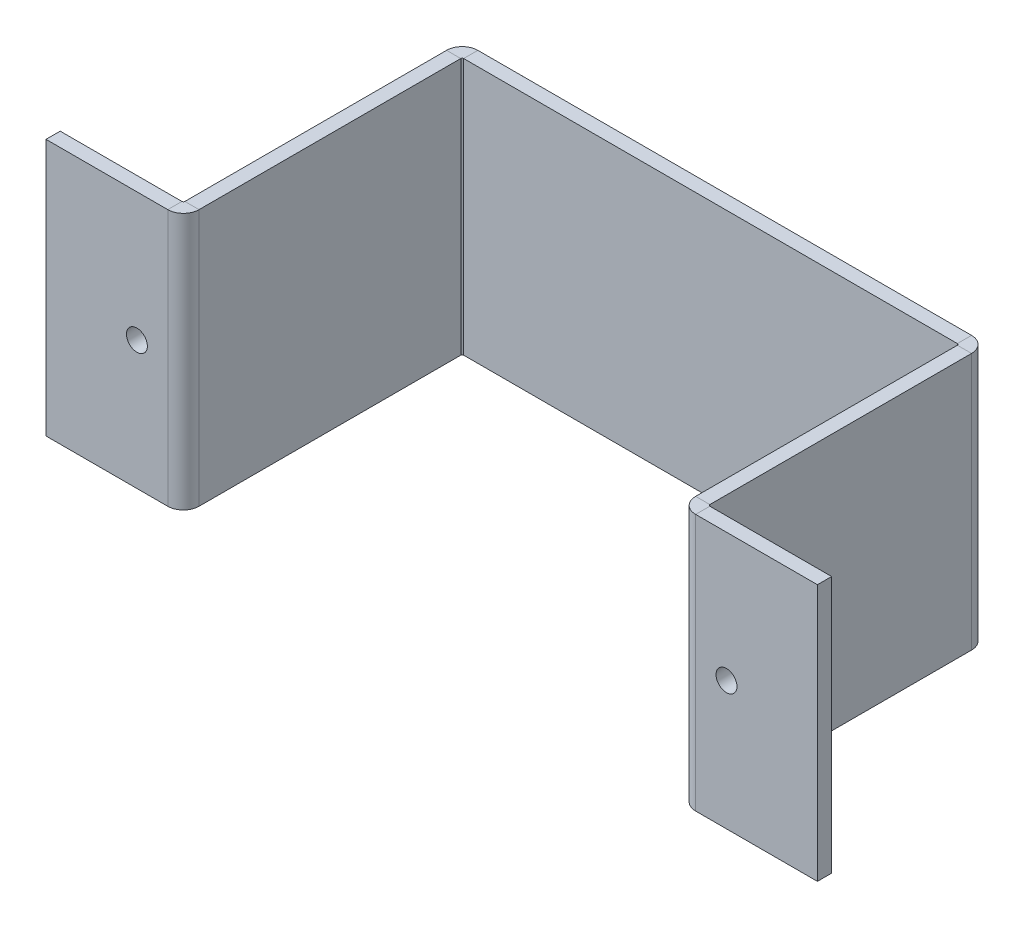
SolidWorks part; units mm, degrees
ref_plane "Front Plane" through (0, 0, 0) normal (0, 0, 1) x (1, 0, 0)
ref_plane "Top Plane" through (0, 0, 0) normal (0, 1, 0) x (1, 0, 0)
ref_plane "Right Plane" through (0, 0, 0) normal (1, 0, 0) x (0, 0, -1)
sketch "Sketch1" plane through (0, 0, 0) normal (0, 1, 0) x (1, 0, 0)
  line L0 (-45.14, 0) -> (-30.89, 0)
  line L1 (-29.89, 1) -> (-29.89, 31.63)
  line L2 (-28.89, 32.63) -> (28.89, 32.63)
  line L3 (0, 43.9351) -> (0, -19.3285) construction
  line L4 (45.14, 0) -> (30.89, 0)
  line L5 (29.89, 1) -> (29.89, 31.63)
  arc A0 (-29.89, 31.63) -> (-28.89, 32.63) centre (-28.89, 31.63) cw
  arc A1 (-30.89, 0) -> (-29.89, 1) centre (-30.89, 1) ccw
  arc A2 (29.89, 31.63) -> (28.89, 32.63) centre (28.89, 31.63) ccw
  arc A3 (30.89, 0) -> (29.89, 1) centre (30.89, 1) cw
  point P9 (-29.89, 32.63)
  point P12 (-29.89, 0)
  point P20 (0, 32.63)
  dimension "D4" = 1
  dimension "D1" = 15.25
  dimension "D2" = 32.63
  dimension "D3" = 29.89
ref_plane "Plane1" through (45.14, 0, 0) normal (1, 0, 0) x (0, 0, -1)
sketch "Sketch2" plane through (45.14, 0, 0) normal (1, 0, 0) x (0, 0, -1)
  line L1 (-0.83, -15.035) -> (0.83, -15.035)
  line L2 (-0.83, -15.035) -> (-0.83, 15.035)
  line L3 (-0.83, 15.035) -> (0.83, 15.035)
  line L4 (0.83, -15.035) -> (0.83, 15.035)
  line L5 (-0.83, -15.035) -> (0.83, 15.035) construction
  line L6 (-0.83, 15.035) -> (0.83, -15.035) construction
  point P0 (0, 0)
  dimension "D1" = 1.66
  dimension "D2" = 30.07
sweep "Sweep1" add profiles "Sketch2" path "Sketch1"
sketch "Sketch3" plane through (0, 0, -0.83) normal (0, 0, -1) x (-1, 0, 0)
  line L0 (-45.14, -15.035) -> (-45.14, 15.035) construction
  circle A0 centre (-34.5, 0) radius 3.175
  circle A1 centre (-34.5, 0) radius 1.225
  dimension "D1" = 10.64
  dimension "D2" = 6.35
  dimension "D3" = 2.45
extrude "Cut-Extrude1" cut sketch "Sketch3" against normal through all contours A1 region at (34.5, 0, -0.83)
extrude "Boss-Extrude1" add sketch "Sketch3<3>" along normal blind 1.43
sketch "Sketch3<3>" plane through (0, 0, -0.83) normal (0, 0, -1) x (-1, 0, 0) same geometry as "Sketch3"
mirror "Mirror1" about plane through (0, 0, 0) normal (1, 0, 0) of "Cut-Extrude1", "Boss-Extrude1"
